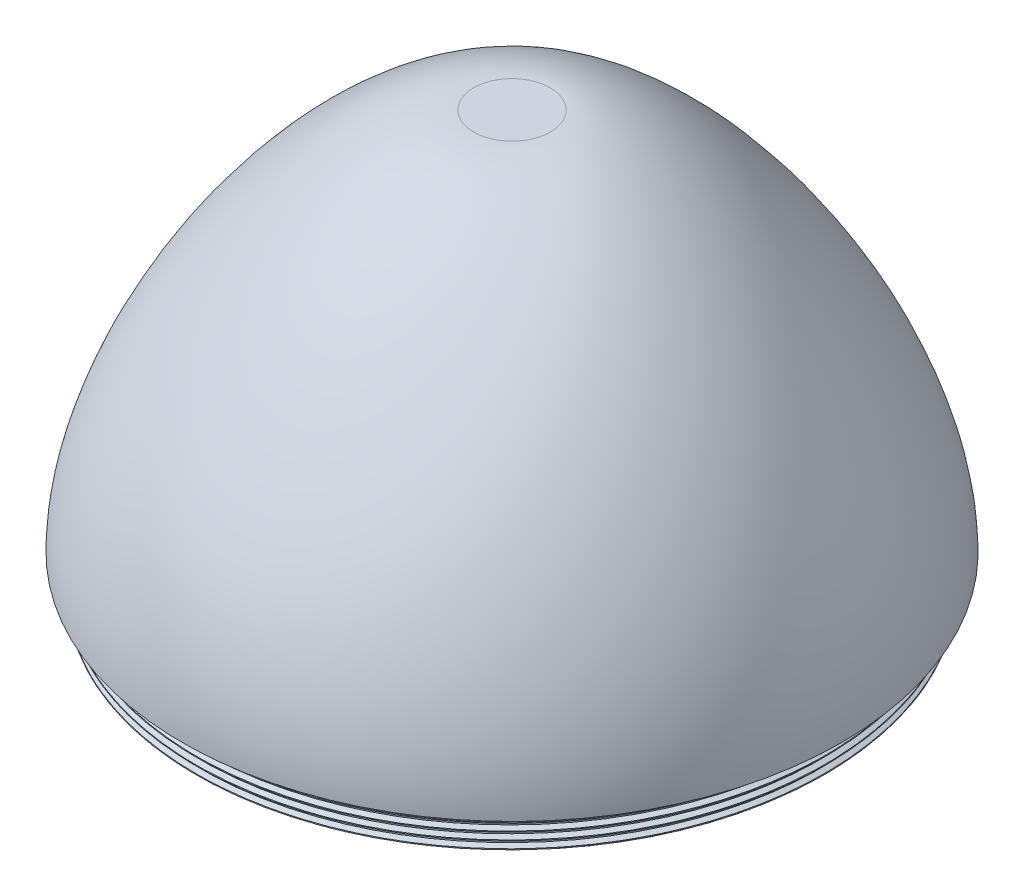
SolidWorks part; units mm, degrees
ref_plane "Front Plane" through (0, 0, 0) normal (0, 0, 1) x (1, 0, 0)
ref_plane "Top Plane" through (0, 0, 0) normal (0, 1, 0) x (1, 0, 0)
ref_plane "Right Plane" through (0, 0, 0) normal (1, 0, 0) x (0, 0, -1)
sketch "Sketch1" plane through (0, 0, 0) normal (0, 0, 1) x (1, 0, 0)
  line L1 (0, 40) -> (0, 0) construction
  line L5 (43, 0) -> (33, 0) construction
  line L6 (0, 40) -> (33, 40) construction
  line L7 (0, 0) -> (33, 0) construction
  line L13 (0, 50) -> (0, 40)
  line L14 (33, 0) -> (33, 40) construction
  line L19 (0, 50) -> (43, 50) construction
  line L20 (43, 50) -> (43, 0) construction
  line L21 (0, 50) -> (5, 50)
  line L22 (43, 0) -> (43, -5) construction
  line L23 (43, -5) -> (41, -5) construction
  line L25 (41, -5) -> (41, 0)
  line L27 (41, -5) -> (39, -5)
  line L32 (41, 0) -> (43, 0)
  line L37 (38, -2.5) -> (38, 0)
  line L38 (33, 0) -> (33, -2.5)
  line L39 (43, -2.5) -> (33, -2.5) construction
  line L40 (33, -2.5) -> (35, -2.5)
  line L42 (36.5, -2.5) -> (38, -2.5)
  line L43 (38, 0) -> (39, 0)
  line L44 (39, 0) -> (39, -5)
  arc A2 (35, -2.5) -> (36.5, -2.5) centre (35.75, -2.5) cw
  conic Q0 (0, 40) -> (33, 0) control (33, 40) rho 0.3
  conic Q1 (5, 50) -> (43, 0) control (43, 50) rho 0.3
  dimension "D2" = 35
  dimension "D3" = 0.75
  dimension "Foam Thickness" = 10
  dimension "Egg Height/2" = 40
  dimension "egg max radius" = 33
  dimension "base radius" = 5
  dimension "outer thread width" = 2
  dimension "thread length" = 5
  dimension "inner thread width" = 2
  dimension "thread distance" = 1
revolve "Revolve1" add sketch "Sketch1" angle 360 about L1
thread "Thread2" pitch 1 method cut trim with end face yes profile "Thread Profile3" start angle 0, offset 0, length 0, pitch 1, diameter 82
ref_plane "Plane3" through (-41, 0, 0) normal (0, 0, 1) x (-1, 0, 0)
sketch "Thread Profile3" plane through (-41, 0, 0) normal (0, 0, 1) x (-1, 0, 0)
  line L0 (0, 0) -> (0, 1) construction
  line L11 (0, 0) -> (0, 0.875)
  line L12 (0, 0.875) -> (-0.5413, 0.5625)
  line L13 (-0.5413, 0.5625) -> (-0.5413, 0.3125)
  line L15 (-0.5413, 0.3125) -> (0, 0)
  line L17 (-0.5413, 0.4375) -> (0, 0.4375) construction
  point P2 (0, 0)
  dimension "Pitch" = 1
  dimension "Profile_Angle" = 60
  dimension "Profile_Land" = 0.25
  dimension "Profile_Height" = 0.5413
